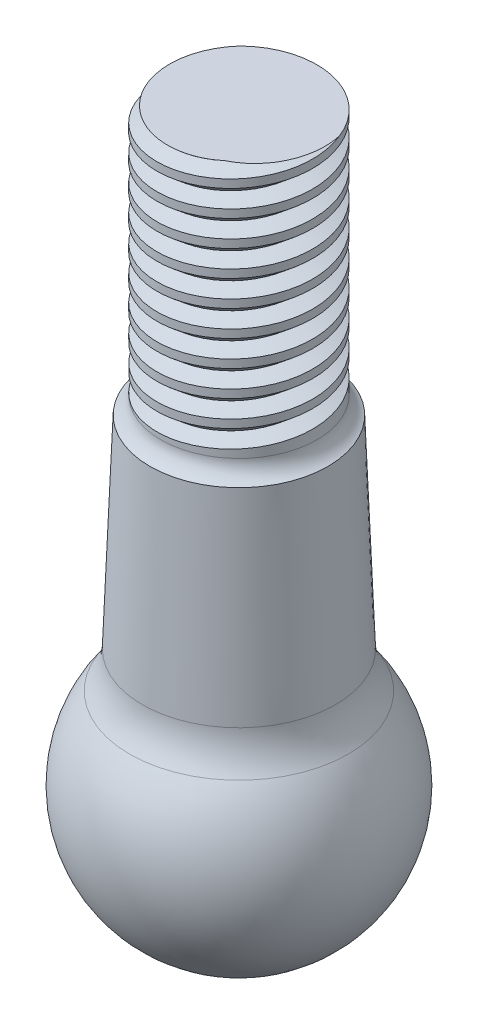
SolidWorks part; units mm, degrees
ref_plane "Front Plane" through (0, 0, 0) normal (0, 0, 1) x (1, 0, 0)
ref_plane "Top Plane" through (0, 0, 0) normal (0, 1, 0) x (1, 0, 0)
ref_plane "Right Plane" through (0, 0, 0) normal (1, 0, 0) x (0, 0, -1)
sketch "Sketch1" plane through (0, 0, 0) normal (1, 0, 0) x (0, 0, -1)
  line L0 (0, 12.9639) -> (0, -14.3693) construction
  line L2 (6, 45) -> (6, 26)
  line L3 (10.5, 0) -> (0, 0) construction
  line L4 (10.5, 0) -> (10.5, 45) construction
  line L5 (10.5, 45) -> (0, 45) construction
  line L6 (0, 0) -> (0, 45) construction
  line L7 (6.8462, 24.65) -> (7.5, 7.3485)
  line L8 (6, 45) -> (0, 45)
  line L9 (0, 45) -> (0, -10.5)
  arc A0 (0, -10.5) -> (0, 10.5) centre (0, 0) ccw construction
  arc A1 (6, 26) -> (6.8462, 24.65) centre (7.5, 26) ccw
  arc A2 (7.5, 7.3485) -> (0, -10.5) centre (0, 0) cw
  point P14 (0, 0)
  dimension "D1" = 21
  dimension "D5" = 1.5
  dimension "D2" = 45
  dimension "D3" = 12
  dimension "D4" = 19
  dimension "D6" = 3
  dimension "D7" = 1.35
revolve "Revolve1" add sketch "Sketch1" angle 360 about L0
sketch "Sketch2" plane through (0, 45, 0) normal (0, 1, 0) x (1, 0, 0)
  circle A1 centre (0, 0) radius 6
  circle A2 centre (0, 0) radius 6
  dimension "D1" = 0
curve "Helix/Spiral1" pitch 2 height 18.5 turns 9.25
ref_plane "Plane2" through (0, 0, 0) normal (1, 0, 0) x (0, 0, -1)
sketch "Sketch3" plane through (0, 0, 0) normal (1, 0, 0) x (0, 0, -1)
  line L1 (-4.8626, 44.8008) -> (-6.3962, 46.0846)
  line L2 (-6.3962, 46.0846) -> (-6.7412, 44.1146)
  line L3 (-6.7412, 44.1146) -> (-4.8626, 44.8008)
  circle A0 centre (-6, 45) radius 0.5774 construction
  spline S0 degree 3 poles (-6, 45) (-6, 44.9586) (-5.6876, 44.8749) (-4.3531, 44.75) (-2.3559, 44.625) (0, 44.5) (2.3559, 44.375) (4.3531, 44.25) (5.6876, 44.125) (6.1562, 44) (5.6876, 43.875) (4.3531, 43.75) (1.6901, 43.5833) (-1.6901, 43.4167) (-4.3531, 43.25) (-5.6876, 43.125) (-6.1562, 43) (-5.6876, 42.875) (-4.3531, 42.75) (-1.6901, 42.5833) (1.6901, 42.4167) (4.3531, 42.25) (5.6876, 42.125) (6.1562, 42) (5.6876, 41.875) (4.3531, 41.75) (1.6901, 41.5833) (-1.6901, 41.4167) (-4.3531, 41.25) (-5.6876, 41.125) (-6.1562, 41) (-5.6876, 40.875) (-4.3531, 40.75) (-1.6901, 40.5833) (1.6901, 40.4167) (4.3531, 40.25) (5.6876, 40.125) (6.1562, 40) (5.6876, 39.875) (4.3531, 39.75) (1.6901, 39.5833) (-1.6901, 39.4167) (-4.3531, 39.25) (-5.6876, 39.125) (-6.1562, 39) (-5.6876, 38.875) (-4.3531, 38.75) (-1.6901, 38.5833) (1.6901, 38.4167) (4.3531, 38.25) (5.6876, 38.125) (6.1562, 38) (5.6876, 37.875) (4.3531, 37.75) (1.6901, 37.5833) (-1.6901, 37.4167) (-4.3531, 37.25) (-5.6876, 37.125) (-6.1562, 37) (-5.6876, 36.875) (-4.3531, 36.75) (-1.6901, 36.5833) (1.6901, 36.4167) (4.3531, 36.25) (5.6876, 36.125) (6.1562, 36) (5.6876, 35.875) (4.3531, 35.75) (1.6901, 35.5833) (-1.6901, 35.4167) (-4.3531, 35.25) (-5.6876, 35.125) (-6.1562, 35) (-5.6876, 34.875) (-4.3531, 34.75) (-1.6901, 34.5833) (1.6901, 34.4167) (4.3531, 34.25) (5.6876, 34.125) (6.1562, 34) (5.6876, 33.875) (4.3531, 33.75) (1.6901, 33.5833) (-1.6901, 33.4167) (-4.3531, 33.25) (-5.6876, 33.125) (-6.1562, 33) (-5.6876, 32.875) (-4.3531, 32.75) (-1.6901, 32.5833) (1.6901, 32.4167) (4.3531, 32.25) (5.6876, 32.125) (6.1562, 32) (5.6876, 31.875) (4.3531, 31.75) (1.6901, 31.5833) (-1.6901, 31.4167) (-4.3531, 31.25) (-5.6876, 31.125) (-6.1562, 31) (-5.6876, 30.875) (-4.3531, 30.75) (-1.6901, 30.5833) (1.6901, 30.4167) (4.3531, 30.25) (5.6876, 30.125) (6.1562, 30) (5.6876, 29.875) (4.3531, 29.75) (1.6901, 29.5833) (-1.6901, 29.4167) (-4.3531, 29.25) (-5.6876, 29.125) (-6.1562, 29) (-5.6876, 28.875) (-4.3531, 28.75) (-1.6901, 28.5833) (1.6901, 28.4167) (4.3531, 28.25) (5.6876, 28.125) (6.1562, 28) (5.6876, 27.875) (4.3531, 27.75) (1.6901, 27.5833) (-1.6901, 27.4167) (-4.3531, 27.25) (-5.6876, 27.125) (-6.1562, 27) (-5.6878, 26.875) (-4.3525, 26.75) (-2.3582, 26.6251) (-0.7804, 26.5414) (0, 26.5) knots 0 0 0 0 0.006757 0.013514 0.02027 0.027027 0.033784 0.040541 0.047297 0.054054 0.060811 0.067568 0.074324 0.087838 0.094595 0.101351 0.108108 0.114865 0.121622 0.128378 0.141892 0.148649 0.155405 0.162162 0.168919 0.175676 0.182432 0.195946 0.202703 0.209459 0.216216 0.222973 0.22973 0.236486 0.25 0.256757 0.263514 0.27027 0.277027 0.283784 0.290541 0.304054 0.310811 0.317568 0.324324 0.331081 0.337838 0.344595 0.358108 0.364865 0.371622 0.378378 0.385135 0.391892 0.398649 0.412162 0.418919 0.425676 0.432432 0.439189 0.445946 0.452703 0.466216 0.472973 0.47973 0.486486 0.493243 0.5 0.506757 0.52027 0.527027 0.533784 0.540541 0.547297 0.554054 0.560811 0.574324 0.581081 0.587838 0.594595 0.601351 0.608108 0.614865 0.628378 0.635135 0.641892 0.648649 0.655405 0.662162 0.668919 0.682432 0.689189 0.695946 0.702703 0.709459 0.716216 0.722973 0.736486 0.743243 0.75 0.756757 0.763514 0.77027 0.777027 0.790541 0.797297 0.804054 0.810811 0.817568 0.824324 0.831081 0.844595 0.851351 0.858108 0.864865 0.871622 0.878378 0.885135 0.898649 0.905405 0.912162 0.918919 0.925676 0.932432 0.939189 0.952703 0.959459 0.966216 0.972973 0.97973 0.986486 0.993243 1 1 1 1 construction
  point P1 (0, 0)
  dimension "D1" = 2
sweep "Cut-Sweep1" cut profiles "Sketch3" path "Helix/Spiral1" align with end faces yes
fillet "Fillet1" radius 5 1 edges at (0, 7.3485, 7.5)
